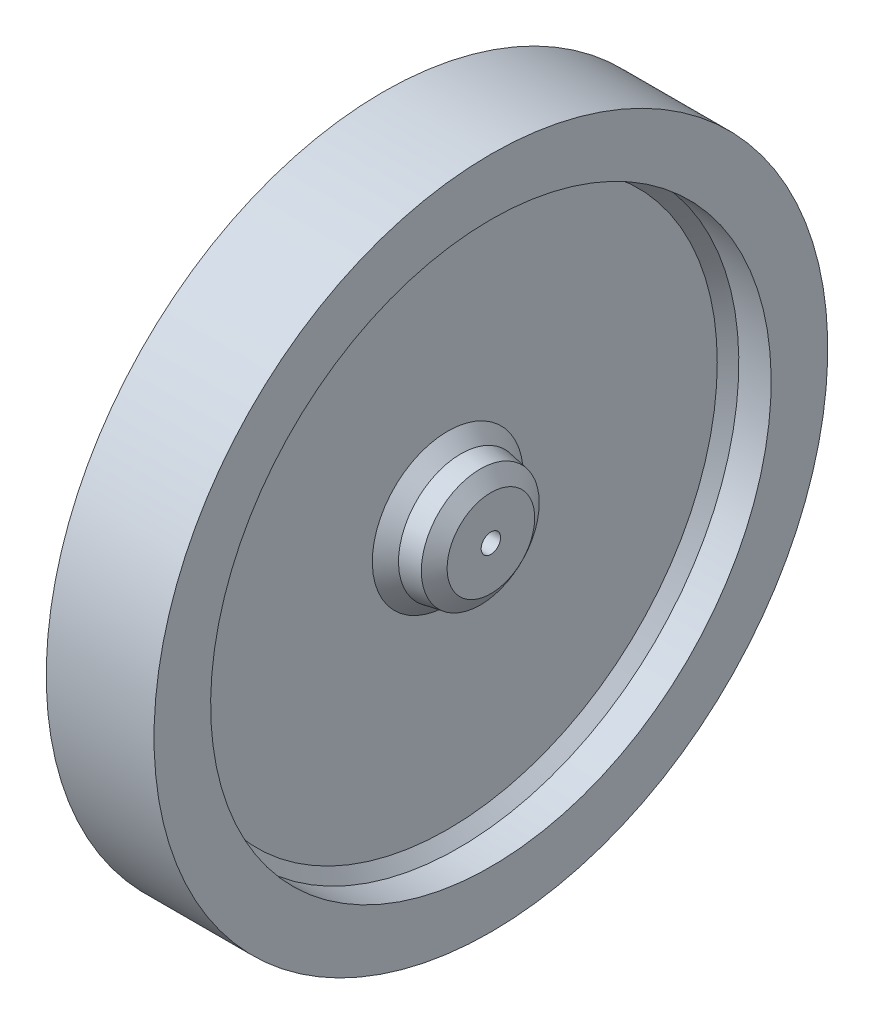
SolidWorks part; units mm, degrees
ref_plane "Front Plane" through (0, 0, 0) normal (0, 0, 1) x (1, 0, 0)
ref_plane "Top Plane" through (0, 0, 0) normal (0, 1, 0) x (1, 0, 0)
ref_plane "Right Plane" through (0, 0, 0) normal (1, 0, 0) x (0, 0, -1)
sketch "Sketch1" plane through (0, 0, 0) normal (0, 0, 1) x (1, 0, 0)
  line L0 (-5, 0) -> (5, 0)
  line L1 (-5, 0) -> (-5, -31.25)
  line L2 (-5, -31.25) -> (5, -31.25)
  line L3 (5, -31.25) -> (5, 0)
  point P3 (0, 0)
  dimension "D1" = 10
  dimension "D2" = 31.25
revolve "Revolve1" add sketch "Sketch1" angle 360 about L0
sketch "Sketch2" plane through (5, 0, 0) normal (1, 0, 0) x (0, 0, -1)
  circle A0 centre (0, 0) radius 26
  dimension "D1" = 52
extrude "Cut-Extrude1" cut sketch "Sketch2" against normal blind 4
sketch "Sketch3" plane through (1, 0, 0) normal (1, 0, 0) x (0, 0, -1)
  circle A0 centre (0, 0) radius 6
  dimension "D1" = 12
extrude "Boss-Extrude1" add sketch "Sketch3" along normal blind 4 draft 10
sketch "Sketch4" plane through (-5, 0, 0) normal (-1, 0, 0) x (0, 0, 1)
  circle A0 centre (0, 0) radius 26
  dimension "D1" = 52
extrude "Cut-Extrude2" cut sketch "Sketch4" against normal blind 4
sketch "Sketch5" plane through (-1, 0, 0) normal (-1, 0, 0) x (0, 0, 1)
  circle A0 centre (0, 0) radius 6
  dimension "D1" = 12
extrude "Boss-Extrude2" add sketch "Sketch5" along normal blind 4 draft 10
chamfer "Chamfer1" distance 1 angle 45 6 edges at (1, 26, 0) (1, 6, 0) (5, 5.2947, 0) (-1, -26, 0) (-5, -5.2947, 0) (-1, -6, 0) first distance on face at (1, 26, 0) first distance on face at (1, 6, 0) first distance on face at (5, 5.2947, 0) first distance on face at (-1, -26, 0) first distance on face at (-5, -5.2947, 0) first distance on face at (-1, -6, 0)
sketch "Sketch6" plane through (-5, 0, 0) normal (-1, 0, 0) x (0, 0, 1)
  circle A0 centre (0, 0) radius 0.9
  dimension "D1" = 1.8
extrude "Cut-Extrude3" cut sketch "Sketch6" against normal through all
